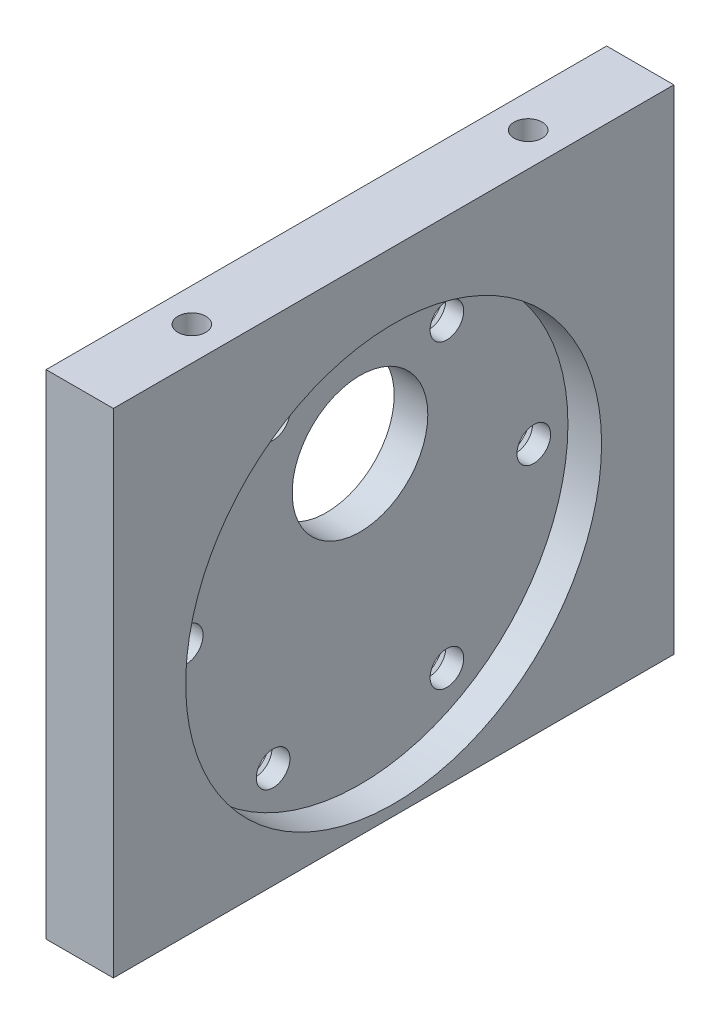
SolidWorks part; units mm, degrees
material "1060 Alloy"
ref_plane "Front Plane" through (0, 0, 0) normal (0, 0, 1) x (1, 0, 0)
ref_plane "Top Plane" through (0, 0, 0) normal (0, 1, 0) x (1, 0, 0)
ref_plane "Right Plane" through (0, 0, 0) normal (1, 0, 0) x (0, 0, -1)
sketch "Sketch1" plane through (0, 0, 0) normal (0, 1, 0) x (1, 0, 0)
  line L1 (0, 0) -> (6, 0)
  line L2 (0, 0) -> (0, 50)
  line L3 (0, 50) -> (6, 50)
  line L4 (6, 0) -> (6, 50)
  dimension "D1" = 50
  dimension "D2" = 6
extrude "Boss-Extrude1" add sketch "Sketch1" along normal blind 44
hole_wizard "Tap Drill for M3 Tap1" positions "Sketch3" profile "Sketch2" hole size "M3" standard "ISO"
sketch "Sketch3" plane through (0, 44, 0) normal (0, 1, 0) x (-1, 0, 0)
  line L0 (0, 0) -> (-6, 0) construction
  line L1 (-6, 0) -> (-6, -50) construction
  line L2 (-6, -50) -> (0, -50) construction
  point P0 (-3, -10)
  point P1 (-3, -40)
  point P6 (-3, -50)
  dimension "D1" = 10
  dimension "D2" = 3
  dimension "D3" = 10
sketch "Sketch2" plane through (3, 44, -10) normal (1, 0, 0) x (0, 0, 1)
  line L0 (0, 0) -> (0, 10.7511)
  line L1 (0, 10.7511) -> (1.25, 10)
  line L2 (1.25, 10) -> (1.25, 0)
  line L5 (1.25, 0) -> (0, 0)
  line L10 (0, 10.7511) -> (-1.25, 10) construction
  line L11 (0, -6.35) -> (0, 107.95) construction
  dimension "Hole Dia." = 2.5
  dimension "Hole Depth" = 10
  dimension "Drill Angle" = 118
hole_wizard "Tap Drill for M3 Tap2" positions "Sketch5" profile "Sketch4" hole size "M3" standard "ISO"
sketch "Sketch5" plane through (0, 0, 0) normal (0, -1, 0) x (1, 0, 0)
  line L0 (6, 0) -> (6, -50) construction
  line L1 (0, 0) -> (6, 0) construction
  line L2 (6, -50) -> (0, -50) construction
  point P0 (3, -10)
  point P1 (3, -40)
  dimension "D1" = 3
  dimension "D2" = 10
  dimension "D3" = 10
sketch "Sketch4" plane through (3, 0, -10) normal (1, 0, 0) x (0, 0, -1)
  line L0 (0, 0) -> (0, 7.7511)
  line L1 (0, 7.7511) -> (1.25, 7)
  line L2 (1.25, 7) -> (1.25, 0)
  line L5 (1.25, 0) -> (0, 0)
  line L10 (0, 7.7511) -> (-1.25, 7) construction
  line L11 (0, -6.35) -> (0, 107.95) construction
  dimension "Hole Dia." = 2.5
  dimension "Hole Depth" = 7
  dimension "Drill Angle" = 118
sketch "Sketch6" plane through (6, 0, 0) normal (1, 0, 0) x (0, 0, -1)
  line L0 (0, 44) -> (0, 0) construction
  line L1 (0, 0) -> (50, 0) construction
  circle A0 centre (25, 19.5) radius 18.55
  dimension "D2" = 37.1
  dimension "D1" = 25
  dimension "D3" = 19.5
extrude "Cut-Extrude1" cut sketch "Sketch6" against normal blind 3
sketch "Sketch7" plane through (3, 0, 0) normal (1, 0, 0) x (0, 0, -1)
  line L1 (6.45, 19.5) -> (25, 19.5) construction
  circle A0 centre (25, 26.5) radius 6.05
  circle A1 centre (25, 19.5) radius 18.55 construction
  circle A3 centre (9.5, 19.5) radius 1.5
  circle A4 centre (25, 19.5) radius 18.55 construction
  dimension "D1" = 12.1
  dimension "D4" = 3
  dimension "D2" = 25
  dimension "D3" = 7
  dimension "D5" = 15.5
extrude "Cut-Extrude2" cut sketch "Sketch7" against normal up to next
pattern_circular "CirPattern1" count 6 over 360 about axis through (6, 19.5, -25) along (1, 0, 0) of face at (3, 19.5, -11)
chamfer "Chamfer1" distance 1.4 angle 45 6 edges at (0, 19.5, -39) (0, 7.3756, -32) (0, 7.3756, -18) (0, 19.5, -11) (0, 31.6244, -18) (0, 31.6244, -32)
